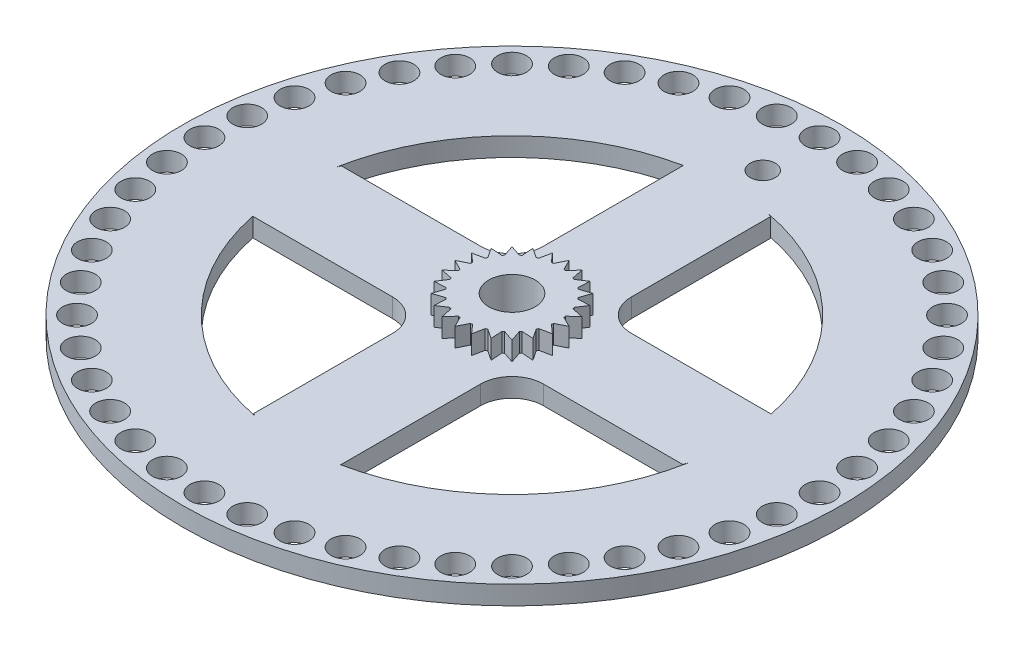
SolidWorks part; units mm, degrees
note: '?' marks a value the reader was unsure of.
ref_plane "Front Plane" through (0, 0, 0) normal (0, 0, 1) x (1, 0, 0)
ref_plane "Top Plane" through (0, 0, 0) normal (0, 1, 0) x (1, 0, 0)
ref_plane "Right Plane" through (0, 0, 0) normal (1, 0, 0) x (0, 0, -1)
sketch "Sketch1" plane through (0, 0, 0) normal (0, 1, 0) x (1, 0, 0)
  circle A0 centre (0, 0) radius 26.25
  dimension "D1" = 52.5
extrude "Boss-Extrude1" add sketch "Sketch1" along normal blind 1.5
sketch "Sketch2" plane through (0, 1.5, 0) normal (0, 1, 0) x (1, 0, 0)
  circle A0 centre (0, 0) radius 17.5
  dimension "D1" = 35
extrude "Cut-Extrude1" cut sketch "Sketch2" against normal blind 4.5
sketch "Sketch3" plane through (0, 1.5, 0) normal (0, 1, 0) x (1, 0, 0)
  line L0 (0, 17.5) -> (0, 26.25) construction
  line L1 (0, 24.5) -> (0, 0)
  circle A50 centre (0, 0) radius 17.5 construction
  circle A51 centre (0, 0) radius 26.25 construction
  circle A98 centre (0, 24.5) radius 1.15
  circle A99 centre (3.1979, 24.2904) radius 1.15
  circle A100 centre (6.3411, 23.6652) radius 1.15
  circle A101 centre (9.3757, 22.635) radius 1.15
  circle A102 centre (12.25, 21.2176) radius 1.15
  circle A103 centre (14.9147, 19.4372) radius 1.15
  circle A104 centre (17.3241, 17.3241) radius 1.15
  circle A105 centre (19.4372, 14.9147) radius 1.15
  circle A106 centre (21.2176, 12.25) radius 1.15
  circle A107 centre (22.635, 9.3757) radius 1.15
  circle A108 centre (23.6652, 6.3411) radius 1.15
  circle A109 centre (24.2904, 3.1979) radius 1.15
  circle A110 centre (24.5, 0) radius 1.15
  circle A111 centre (24.2904, -3.1979) radius 1.15
  circle A112 centre (23.6652, -6.3411) radius 1.15
  circle A113 centre (22.635, -9.3757) radius 1.15
  circle A114 centre (21.2176, -12.25) radius 1.15
  circle A115 centre (19.4372, -14.9147) radius 1.15
  circle A116 centre (17.3241, -17.3241) radius 1.15
  circle A117 centre (14.9147, -19.4372) radius 1.15
  circle A118 centre (12.25, -21.2176) radius 1.15
  circle A119 centre (9.3757, -22.635) radius 1.15
  circle A120 centre (6.3411, -23.6652) radius 1.15
  circle A121 centre (3.1979, -24.2904) radius 1.15
  circle A122 centre (0, -24.5) radius 1.15
  circle A123 centre (-3.1979, -24.2904) radius 1.15
  circle A124 centre (-6.3411, -23.6652) radius 1.15
  circle A125 centre (-9.3757, -22.635) radius 1.15
  circle A126 centre (-12.25, -21.2176) radius 1.15
  circle A127 centre (-14.9147, -19.4372) radius 1.15
  circle A128 centre (-17.3241, -17.3241) radius 1.15
  circle A129 centre (-19.4372, -14.9147) radius 1.15
  circle A130 centre (-21.2176, -12.25) radius 1.15
  circle A131 centre (-22.635, -9.3757) radius 1.15
  circle A132 centre (-23.6652, -6.3411) radius 1.15
  circle A133 centre (-24.2904, -3.1979) radius 1.15
  circle A134 centre (-24.5, 0) radius 1.15
  circle A135 centre (-24.2904, 3.1979) radius 1.15
  circle A136 centre (-23.6652, 6.3411) radius 1.15
  circle A137 centre (-22.635, 9.3757) radius 1.15
  circle A138 centre (-21.2176, 12.25) radius 1.15
  circle A139 centre (-19.4372, 14.9147) radius 1.15
  circle A140 centre (-17.3241, 17.3241) radius 1.15
  circle A141 centre (-14.9147, 19.4372) radius 1.15
  circle A142 centre (-12.25, 21.2176) radius 1.15
  circle A143 centre (-9.3757, 22.635) radius 1.15
  circle A144 centre (-6.3411, 23.6652) radius 1.15
  circle A145 centre (-3.1979, 24.2904) radius 1.15
  point P105 (0, 0)
  point P109 (0, 0)
  dimension "D1" = 24.5
  dimension "D2" = 48
  dimension "D3" = 2.3
extrude "Cut-Extrude2" cut sketch "Sketch3" against normal blind 2.5
sketch "Sketch4" plane through (0, 1.5, 0) normal (0, 1, 0) x (1, 0, 0)
  line L0 (0, 17.5) -> (-1, 17.5)
  line L4 (-1, 17.5) -> (0, 15.3267)
  line L196 (0, 15.3267) -> (1, 17.5)
  line L197 (1, 17.5) -> (0, 17.5)
  line L200 (3.5971, 17.1555) -> (2.6082, 17.3045)
  line L201 (2.6082, 17.3045) -> (1.6194, 17.4536)
  line L202 (1.6194, 17.4536) -> (2.2843, 15.1555)
  line L203 (2.2843, 15.1555) -> (3.5971, 17.1555)
  line L204 (6.1138, 16.4278) -> (5.1582, 16.7225)
  line L205 (5.1582, 16.7225) -> (4.2026, 17.0173)
  line L345 (4.2026, 17.0173) -> (4.5176, 14.6458)
  line L346 (4.5176, 14.6458) -> (6.1138, 16.4278)
  line L347 (8.4939, 15.3331) -> (7.593, 15.767)
  line L348 (7.593, 15.767) -> (6.692, 16.2008)
  line L349 (6.692, 16.2008) -> (6.65, 13.8089)
  line L350 (6.65, 13.8089) -> (8.4939, 15.3331)
  line L351 (10.6843, 13.8959) -> (9.8581, 14.4592)
  line L352 (9.8581, 14.4592) -> (9.0319, 15.0225)
  line L353 (9.0319, 15.0225) -> (8.6338, 12.6635)
  line L354 (8.6338, 12.6635) -> (10.6843, 13.8959)
  line L355 (12.6361, 12.1482) -> (11.903, 12.8284)
  line L356 (11.903, 12.8284) -> (11.17, 13.5086)
  line L357 (11.17, 13.5086) -> (10.4248, 11.2353)
  line L358 (10.4248, 11.2353) -> (12.6361, 12.1482)
  line L359 (14.3055, 10.1292) -> (13.6821, 10.9111)
  line L360 (13.6821, 10.9111) -> (13.0586, 11.6929)
  line L361 (13.0586, 11.6929) -> (11.9829, 9.5561)
  line L362 (11.9829, 9.5561) -> (14.3055, 10.1292)
  line L363 (15.6554, 7.884) -> (15.1554, 8.75)
  line L364 (15.1554, 8.75) -> (14.6554, 9.616)
  line L365 (14.6554, 9.616) -> (13.2733, 7.6634)
  line L366 (13.2733, 7.6634) -> (15.6554, 7.884)
  line L367 (16.6556, 5.4626) -> (16.2903, 6.3935)
  line L368 (16.2903, 6.3935) -> (15.9249, 7.3243)
  line L369 (15.9249, 7.3243) -> (14.2672, 5.5995)
  line L370 (14.2672, 5.5995) -> (16.6556, 5.4626)
  line L371 (17.2838, 2.9192) -> (17.0612, 3.8941)
  line L372 (17.0612, 3.8941) -> (16.8387, 4.869)
  line L373 (16.8387, 4.869) -> (14.9424, 3.4105)
  line L374 (14.9424, 3.4105) -> (17.2838, 2.9192)
  line L375 (17.5258, 0.3106) -> (17.4511, 1.3078)
  line L376 (17.4511, 1.3078) -> (17.3763, 2.305)
  line L377 (17.3763, 2.305) -> (15.2839, 1.1454)
  line L378 (15.2839, 1.1454) -> (17.5258, 0.3106)
  line L379 (17.3763, -2.305) -> (17.4511, -1.3078)
  line L380 (17.4511, -1.3078) -> (17.5258, -0.3106)
  line L381 (17.5258, -0.3106) -> (15.2839, -1.1454)
  line L382 (15.2839, -1.1454) -> (17.3763, -2.305)
  line L383 (16.8387, -4.869) -> (17.0612, -3.8941)
  line L384 (17.0612, -3.8941) -> (17.2838, -2.9192)
  line L385 (17.2838, -2.9192) -> (14.9424, -3.4105)
  line L386 (14.9424, -3.4105) -> (16.8387, -4.869)
  line L387 (15.9249, -7.3243) -> (16.2903, -6.3935)
  line L388 (16.2903, -6.3935) -> (16.6556, -5.4626)
  line L389 (16.6556, -5.4626) -> (14.2672, -5.5995)
  line L390 (14.2672, -5.5995) -> (15.9249, -7.3243)
  line L391 (14.6554, -9.616) -> (15.1554, -8.75)
  line L392 (15.1554, -8.75) -> (15.6554, -7.884)
  line L393 (15.6554, -7.884) -> (13.2733, -7.6634)
  line L394 (13.2733, -7.6634) -> (14.6554, -9.616)
  line L395 (13.0586, -11.6929) -> (13.6821, -10.9111)
  line L396 (13.6821, -10.9111) -> (14.3055, -10.1292)
  line L397 (14.3055, -10.1292) -> (11.9829, -9.5561)
  line L398 (11.9829, -9.5561) -> (13.0586, -11.6929)
  line L399 (11.17, -13.5086) -> (11.903, -12.8284)
  line L400 (11.903, -12.8284) -> (12.6361, -12.1482)
  line L401 (12.6361, -12.1482) -> (10.4248, -11.2353)
  line L402 (10.4248, -11.2353) -> (11.17, -13.5086)
  line L403 (9.0319, -15.0225) -> (9.8581, -14.4592)
  line L404 (9.8581, -14.4592) -> (10.6843, -13.8959)
  line L405 (10.6843, -13.8959) -> (8.6338, -12.6635)
  line L406 (8.6338, -12.6635) -> (9.0319, -15.0225)
  line L407 (6.692, -16.2008) -> (7.593, -15.767)
  line L408 (7.593, -15.767) -> (8.4939, -15.3331)
  line L409 (8.4939, -15.3331) -> (6.65, -13.8089)
  line L410 (6.65, -13.8089) -> (6.692, -16.2008)
  line L411 (4.2026, -17.0173) -> (5.1582, -16.7225)
  line L412 (5.1582, -16.7225) -> (6.1138, -16.4278)
  line L413 (6.1138, -16.4278) -> (4.5176, -14.6458)
  line L414 (4.5176, -14.6458) -> (4.2026, -17.0173)
  line L527 (0, 17.5) -> (0, 14.3872) construction
  line L528 (1.6194, -17.4536) -> (2.6082, -17.3045)
  line L529 (2.6082, -17.3045) -> (3.5971, -17.1555)
  line L530 (3.5971, -17.1555) -> (2.2843, -15.1555)
  line L531 (2.2843, -15.1555) -> (1.6194, -17.4536)
  line L532 (-1, -17.5) -> (0, -17.5)
  line L533 (0, -17.5) -> (1, -17.5)
  line L534 (1, -17.5) -> (0, -15.3267)
  line L535 (0, -15.3267) -> (-1, -17.5)
  line L536 (-3.5971, -17.1555) -> (-2.6082, -17.3045)
  line L537 (-2.6082, -17.3045) -> (-1.6194, -17.4536)
  line L538 (-1.6194, -17.4536) -> (-2.2843, -15.1555)
  line L539 (-2.2843, -15.1555) -> (-3.5971, -17.1555)
  line L540 (-6.1138, -16.4278) -> (-5.1582, -16.7225)
  line L541 (-5.1582, -16.7225) -> (-4.2026, -17.0173)
  line L542 (-4.2026, -17.0173) -> (-4.5176, -14.6458)
  line L543 (-4.5176, -14.6458) -> (-6.1138, -16.4278)
  line L544 (-8.4939, -15.3331) -> (-7.593, -15.767)
  line L545 (-7.593, -15.767) -> (-6.692, -16.2008)
  line L546 (-6.692, -16.2008) -> (-6.65, -13.8089)
  line L547 (-6.65, -13.8089) -> (-8.4939, -15.3331)
  line L548 (-10.6843, -13.8959) -> (-9.8581, -14.4592)
  line L549 (-9.8581, -14.4592) -> (-9.0319, -15.0225)
  line L550 (-9.0319, -15.0225) -> (-8.6338, -12.6635)
  line L551 (-8.6338, -12.6635) -> (-10.6843, -13.8959)
  line L552 (-12.6361, -12.1482) -> (-11.903, -12.8284)
  line L553 (-11.903, -12.8284) -> (-11.17, -13.5086)
  line L554 (-11.17, -13.5086) -> (-10.4248, -11.2353)
  line L555 (-10.4248, -11.2353) -> (-12.6361, -12.1482)
  line L556 (-14.3055, -10.1292) -> (-13.6821, -10.9111)
  line L557 (-13.6821, -10.9111) -> (-13.0586, -11.6929)
  line L558 (-13.0586, -11.6929) -> (-11.9829, -9.5561)
  line L559 (-11.9829, -9.5561) -> (-14.3055, -10.1292)
  line L560 (-15.6554, -7.884) -> (-15.1554, -8.75)
  line L561 (-15.1554, -8.75) -> (-14.6554, -9.616)
  line L562 (-14.6554, -9.616) -> (-13.2733, -7.6634)
  line L563 (-13.2733, -7.6634) -> (-15.6554, -7.884)
  line L564 (-16.6556, -5.4626) -> (-16.2903, -6.3935)
  line L565 (-16.2903, -6.3935) -> (-15.9249, -7.3243)
  line L566 (-15.9249, -7.3243) -> (-14.2672, -5.5995)
  line L567 (-14.2672, -5.5995) -> (-16.6556, -5.4626)
  line L568 (-17.2838, -2.9192) -> (-17.0612, -3.8941)
  line L569 (-17.0612, -3.8941) -> (-16.8387, -4.869)
  line L570 (-16.8387, -4.869) -> (-14.9424, -3.4105)
  line L571 (-14.9424, -3.4105) -> (-17.2838, -2.9192)
  line L572 (-17.5258, -0.3106) -> (-17.4511, -1.3078)
  line L573 (-17.4511, -1.3078) -> (-17.3763, -2.305)
  line L574 (-17.3763, -2.305) -> (-15.2839, -1.1454)
  line L575 (-15.2839, -1.1454) -> (-17.5258, -0.3106)
  line L576 (-17.3763, 2.305) -> (-17.4511, 1.3078)
  line L577 (-17.4511, 1.3078) -> (-17.5258, 0.3106)
  line L578 (-17.5258, 0.3106) -> (-15.2839, 1.1454)
  line L579 (-15.2839, 1.1454) -> (-17.3763, 2.305)
  line L580 (-16.8387, 4.869) -> (-17.0612, 3.8941)
  line L581 (-17.0612, 3.8941) -> (-17.2838, 2.9192)
  line L582 (-17.2838, 2.9192) -> (-14.9424, 3.4105)
  line L583 (-14.9424, 3.4105) -> (-16.8387, 4.869)
  line L584 (-15.9249, 7.3243) -> (-16.2903, 6.3935)
  line L585 (-16.2903, 6.3935) -> (-16.6556, 5.4626)
  line L586 (-16.6556, 5.4626) -> (-14.2672, 5.5995)
  line L587 (-14.2672, 5.5995) -> (-15.9249, 7.3243)
  line L588 (-14.6554, 9.616) -> (-15.1554, 8.75)
  line L589 (-15.1554, 8.75) -> (-15.6554, 7.884)
  line L590 (-15.6554, 7.884) -> (-13.2733, 7.6634)
  line L591 (-13.2733, 7.6634) -> (-14.6554, 9.616)
  line L592 (-13.0586, 11.6929) -> (-13.6821, 10.9111)
  line L593 (-13.6821, 10.9111) -> (-14.3055, 10.1292)
  line L594 (-14.3055, 10.1292) -> (-11.9829, 9.5561)
  line L595 (-11.9829, 9.5561) -> (-13.0586, 11.6929)
  line L596 (-11.17, 13.5086) -> (-11.903, 12.8284)
  line L597 (-11.903, 12.8284) -> (-12.6361, 12.1482)
  line L598 (-12.6361, 12.1482) -> (-10.4248, 11.2353)
  line L599 (-10.4248, 11.2353) -> (-11.17, 13.5086)
  line L600 (-9.0319, 15.0225) -> (-9.8581, 14.4592)
  line L601 (-9.8581, 14.4592) -> (-10.6843, 13.8959)
  line L602 (-10.6843, 13.8959) -> (-8.6338, 12.6635)
  line L603 (-8.6338, 12.6635) -> (-9.0319, 15.0225)
  line L604 (-6.692, 16.2008) -> (-7.593, 15.767)
  line L605 (-7.593, 15.767) -> (-8.4939, 15.3331)
  line L606 (-8.4939, 15.3331) -> (-6.65, 13.8089)
  line L607 (-6.65, 13.8089) -> (-6.692, 16.2008)
  line L608 (-4.2026, 17.0173) -> (-5.1582, 16.7225)
  line L609 (-5.1582, 16.7225) -> (-6.1138, 16.4278)
  line L610 (-6.1138, 16.4278) -> (-4.5176, 14.6458)
  line L611 (-4.5176, 14.6458) -> (-4.2026, 17.0173)
  line L612 (-1.6194, 17.4536) -> (-2.6082, 17.3045)
  line L613 (-2.6082, 17.3045) -> (-3.5971, 17.1555)
  line L614 (-3.5971, 17.1555) -> (-2.2843, 15.1555)
  line L615 (-2.2843, 15.1555) -> (-1.6194, 17.4536)
  circle A50 centre (0, 0) radius 17.5 construction
  point P199 (0, 0)
  dimension "D1" = 1
  dimension "D2" = 1
  dimension "D3" = 42
extrude "Boss-Extrude3" [suppressed] add sketch "Sketch4" against normal up to surface (1.5 mm away)
ref_axis "Axis1" through (0, 0, -24.5) along (0, 1, 0)?
sketch "Sketch5" plane through (0, 1.5, 0) normal (0, 1, 0) x (1, 0, 0)
  circle A0 centre (0, 19.9721) radius 1
  dimension "D1" = 2
extrude "Cut-Extrude3" cut sketch "Sketch5" against normal up to surface (1.5 mm away) up to face at (-12.25, 0, -20.0676)
sketch "Sketch6" plane through (0, 1.5, 0) normal (0, 1, 0) x (1, 0, 0)
  line L0 (-3.5, 6) -> (-3.5, 17.1464)
  line L1 (6, 3.5) -> (17.1464, 3.5)
  line L2 (3.5, 6) -> (3.5, 17.0942)
  line L3 (3.5, -6) -> (3.5, -17.1464)
  line L4 (6, -3.5) -> (17.0942, -3.5)
  line L5 (-6, -3.5) -> (-17.1464, -3.5)
  line L6 (-3.5, -6) -> (-3.5, -17.0942)
  line L7 (-6, 3.5) -> (-17.0942, 3.5)
  line L8 (-3.5, 17.1464) -> (0, 18.4475)
  line L9 (0, 18.4475) -> (3.5, 17.0942)
  line L10 (17.1464, 3.5) -> (18.4475, 0)
  line L11 (18.4475, 0) -> (17.0942, -3.5)
  line L12 (3.5, -17.1464) -> (0, -18.4475)
  line L13 (0, -18.4475) -> (-3.5, -17.0942)
  line L14 (-17.1464, -3.5) -> (-18.4475, 0)
  line L15 (-18.4475, 0) -> (-17.0942, 3.5)
  line L16 (0, 0) -> (0, 21.9816)
  circle A0 centre (0, 0) radius 3.5 construction
  circle A1 centre (0, 0) radius 17.5 construction
  arc A2 (-6, 3.5) -> (-3.5, 6) centre (-6, 6) ccw
  arc A3 (3.5, 6) -> (6, 3.5) centre (6, 6) ccw
  arc A4 (6, -3.5) -> (3.5, -6) centre (6, -6) ccw
  arc A5 (-3.5, -6) -> (-6, -3.5) centre (-6, -6) ccw
  point P24 (0, 0)
  point P29 (0, 0)
  dimension "D1" = 4
  dimension "D2" = 2.5
  dimension "D3" = 3.5
  dimension "D4" = 3.5
extrude "Boss-Extrude4" add sketch "Sketch6" against normal up to surface (1.5 mm away) contours L7 L15 L14 L5 A5 L6 L13 L12 L3 A4 L4 L11 L10 L1 A3 L2 L9 L8 L0 A2 up to face at (0, 0, -18.9721)
sketch "Sketch12" plane through (0, 1.5, 0) normal (0, 1, 0) x (1, 0, 0)
  circle A0 centre (0, 0) radius 3.75
  dimension "D1" = 7.5
extrude "Boss-Extrude6" add sketch "Sketch12" along normal blind 1.5
sketch "Sketch7" plane through (0, 1.5, 0) normal (0, 1, 0) x (1, 0, 0)
  circle A0 centre (0, 0) radius 1.85
  dimension "D1" = 3.7
extrude "Cut-Extrude4" cut sketch "Sketch7" against normal up to surface (1.5 mm away) and the other way blind 11 up to face at (6.9888, 0, -9.7798)
sketch "Sketch11" plane through (0, 1.5, 0) normal (0, 1, 0) x (1, 0, 0)
  circle A0 centre (0, 0) radius 1.75 construction
sketch "Sketch15" plane through (0, 1.5, 0) normal (0, 1, 0) x (1, 0, 0)
  line L37 (0, 3.75) -> (0, 3.65) construction
  line L115 (0.45, 3.65) -> (-0.45, 3.65)
  line L116 (-0.45, 3.65) -> (0, 4.55)
  line L117 (0.45, 3.65) -> (0, 4.55)
  line L118 (1.3794, 3.4092) -> (0.51, 3.6421)
  line L119 (0.51, 3.6421) -> (1.1776, 4.395)
  line L120 (1.3794, 3.4092) -> (1.1776, 4.395)
  line L121 (2.2147, 2.936) -> (1.4353, 3.386)
  line L122 (1.4353, 3.386) -> (2.275, 3.9404)
  line L123 (2.2147, 2.936) -> (2.275, 3.9404)
  line L124 (2.8991, 2.2627) -> (2.2627, 2.8991)
  line L125 (2.2627, 2.8991) -> (3.2173, 3.2173)
  line L126 (2.8991, 2.2627) -> (3.2173, 3.2173)
  line L127 (3.386, 1.4353) -> (2.936, 2.2147)
  line L128 (2.936, 2.2147) -> (3.9404, 2.275)
  line L129 (3.386, 1.4353) -> (3.9404, 2.275)
  line L130 (3.6421, 0.51) -> (3.4092, 1.3794)
  line L131 (3.4092, 1.3794) -> (4.395, 1.1776)
  line L132 (3.6421, 0.51) -> (4.395, 1.1776)
  line L133 (3.65, -0.45) -> (3.65, 0.45)
  line L134 (3.65, 0.45) -> (4.55, 0)
  line L135 (3.65, -0.45) -> (4.55, 0)
  line L136 (3.4092, -1.3794) -> (3.6421, -0.51)
  line L137 (3.6421, -0.51) -> (4.395, -1.1776)
  line L138 (3.4092, -1.3794) -> (4.395, -1.1776)
  line L139 (2.936, -2.2147) -> (3.386, -1.4353)
  line L140 (3.386, -1.4353) -> (3.9404, -2.275)
  line L141 (2.936, -2.2147) -> (3.9404, -2.275)
  line L142 (2.2627, -2.8991) -> (2.8991, -2.2627)
  line L143 (2.8991, -2.2627) -> (3.2173, -3.2173)
  line L144 (2.2627, -2.8991) -> (3.2173, -3.2173)
  line L145 (1.4353, -3.386) -> (2.2147, -2.936)
  line L146 (2.2147, -2.936) -> (2.275, -3.9404)
  line L147 (1.4353, -3.386) -> (2.275, -3.9404)
  line L148 (0.51, -3.6421) -> (1.3794, -3.4092)
  line L149 (1.3794, -3.4092) -> (1.1776, -4.395)
  line L150 (0.51, -3.6421) -> (1.1776, -4.395)
  line L151 (-0.45, -3.65) -> (0.45, -3.65)
  line L152 (0.45, -3.65) -> (0, -4.55)
  line L153 (-0.45, -3.65) -> (0, -4.55)
  line L154 (-1.3794, -3.4092) -> (-0.51, -3.6421)
  line L155 (-0.51, -3.6421) -> (-1.1776, -4.395)
  line L156 (-1.3794, -3.4092) -> (-1.1776, -4.395)
  line L157 (-2.2147, -2.936) -> (-1.4353, -3.386)
  line L158 (-1.4353, -3.386) -> (-2.275, -3.9404)
  line L159 (-2.2147, -2.936) -> (-2.275, -3.9404)
  line L160 (-2.8991, -2.2627) -> (-2.2627, -2.8991)
  line L161 (-2.2627, -2.8991) -> (-3.2173, -3.2173)
  line L162 (-2.8991, -2.2627) -> (-3.2173, -3.2173)
  line L163 (-3.386, -1.4353) -> (-2.936, -2.2147)
  line L164 (-2.936, -2.2147) -> (-3.9404, -2.275)
  line L165 (-3.386, -1.4353) -> (-3.9404, -2.275)
  line L166 (-3.6421, -0.51) -> (-3.4092, -1.3794)
  line L167 (-3.4092, -1.3794) -> (-4.395, -1.1776)
  line L168 (-3.6421, -0.51) -> (-4.395, -1.1776)
  line L169 (-3.65, 0.45) -> (-3.65, -0.45)
  line L170 (-3.65, -0.45) -> (-4.55, 0)
  line L171 (-3.65, 0.45) -> (-4.55, 0)
  line L172 (-3.4092, 1.3794) -> (-3.6421, 0.51)
  line L173 (-3.6421, 0.51) -> (-4.395, 1.1776)
  line L174 (-3.4092, 1.3794) -> (-4.395, 1.1776)
  line L175 (-2.936, 2.2147) -> (-3.386, 1.4353)
  line L176 (-3.386, 1.4353) -> (-3.9404, 2.275)
  line L177 (-2.936, 2.2147) -> (-3.9404, 2.275)
  line L178 (-2.2627, 2.8991) -> (-2.8991, 2.2627)
  line L179 (-2.8991, 2.2627) -> (-3.2173, 3.2173)
  line L180 (-2.2627, 2.8991) -> (-3.2173, 3.2173)
  line L181 (-1.4353, 3.386) -> (-2.2147, 2.936)
  line L182 (-2.2147, 2.936) -> (-2.275, 3.9404)
  line L183 (-1.4353, 3.386) -> (-2.275, 3.9404)
  line L184 (-0.51, 3.6421) -> (-1.3794, 3.4092)
  line L185 (-1.3794, 3.4092) -> (-1.1776, 4.395)
  line L186 (-0.51, 3.6421) -> (-1.1776, 4.395)
  line L259 (0, 3.75) -> (0, 4.55)
  circle A1 centre (0, 0) radius 3.75 construction
  point P153 (0, 0)
  dimension "D1" = 0.1
  dimension "D2" = 0.45
  dimension "D4" = 0.8
  dimension "D3" = 24
extrude "Boss-Extrude8" add sketch "Sketch15" along normal up to surface (1.5 mm away)
